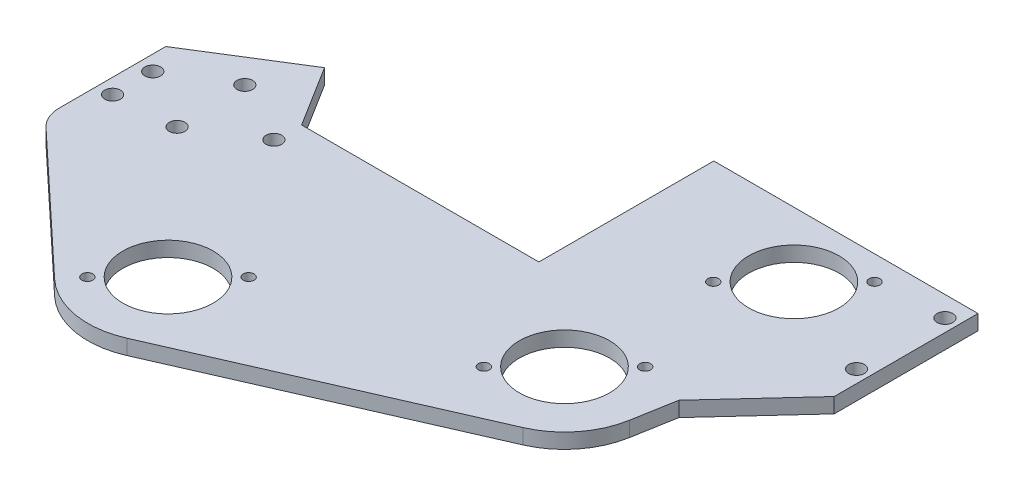
SolidWorks part; units mm, degrees
ref_plane "Front Plane" through (0, 0, 0) normal (0, 0, 1) x (1, 0, 0)
ref_plane "Top Plane" through (0, 0, 0) normal (0, 1, 0) x (1, 0, 0)
ref_plane "Right Plane" through (0, 0, 0) normal (1, 0, 0) x (0, 0, -1)
sketch "Sketch1" plane through (0, 0, 0) normal (0, 1, 0) x (1, 0, 0)
  line L1 (-62.0382, -79.8833) -> (25.1671, -41.6958)
  line L5 (39.9402, -22.8907) -> (42.2751, -9.5867)
  line L6 (42.2751, -9.5867) -> (65.831, 16.0128)
  line L12 (-135.7544, -31.9237) -> (-135.7544, 6.1763)
  line L16 (-92.7762, 6.1643) -> (-17.7344, 6.1643)
  line L17 (-135.7544, -31.9237) -> (-89.5888, -75.1562)
  line L19 (65.831, 61.4936) -> (-17.7344, 61.4936)
  line L20 (65.831, 16.0128) -> (65.831, 61.4936)
  line L22 (-17.7344, 61.4936) -> (-17.7344, 6.1643)
  line L23 (-135.7544, 6.1763) -> (-104.8504, 25.4872)
  line L24 (-218.6325, 207.5765) -> (-71.6498, -27.6449) construction
  line L25 (-104.8504, 25.4872) -> (-92.7762, 6.1643)
  line L26 (-72.2583, -56.6285) -> (15.031, -18.5085) construction
  line L27 (-72.2269, -82.0164) -> (109.3231, -82.0164) construction
  line L28 (15.0167, -18.5164) -> (15.0167, -82.0164) construction
  circle A0 centre (28.0466, 41.0458) radius 14.29
  circle A1 centre (15.031, -18.5085) radius 14.29
  circle A2 centre (-72.2583, -56.6285) radius 14.29
  arc A4 (39.9402, -22.8907) -> (25.1671, -41.6958) centre (15.0167, -18.5164) cw
  arc A6 (-62.0382, -79.8833) -> (-89.5888, -75.1562) centre (-72.2269, -56.6164) cw
  circle A7 centre (15.031, -18.5085) radius 25.4 construction
  circle A8 centre (-72.2583, -56.6285) radius 25.4 construction
  circle A9 centre (-28.6137, -37.5685) radius 22.225 construction
  circle A10 centre (28.0466, 41.0458) radius 30.48 construction
  circle A11 centre (15.031, -18.5085) radius 30.48 construction
  point P11 (-62.0382, -79.8833)
  point P34 (15.0167, -18.5164)
  point P35 (28.0466, 41.0458)
  dimension "D2" = 50.8
  dimension "D3" = 50.8
  dimension "D4" = 44.45
  dimension "D5" = 63.5
  dimension "D7" = 60.96
  dimension "D8" = 60.96
  dimension "D1" = 140.0048
  dimension "D6" = 95.25
  dimension "D9" = 50.8
  dimension "D10" = 143.51
extrude "Boss-Extrude1" add sketch "Sketch1" along normal blind 4.7625
fillet "Fillet1" radius 10 1 edges at (-135.7544, 2.3813, 31.9237)
hole_wizard "#10 Clearance Hole1" positions "Sketch2" profile "Sketch3" hole size "#10" standard "ANSI Inch" end condition through all
sketch "Sketch2" plane through (0, 4.7625, 0) normal (0, 1, 0) x (1, 0, 0)
  point P0 (61.8305, 55.0158)
  point P3 (61.8305, 27.0758)
  point P7 (-130.9919, -2.7257)
  point P10 (-130.9919, -15.4257)
sketch "Sketch3" plane through (61.8305, 4.7625, -55.0158) normal (1, 0, 0) x (0, 0, 1)
  line L0 (0, 0) -> (0, 4.7625)
  line L1 (0, 4.7625) -> (2.4892, 4.7625)
  line L2 (2.4892, 4.7625) -> (2.4892, 0)
  line L5 (2.4892, 0) -> (0, 0)
  line L11 (0, -6.35) -> (0, 107.95) construction
  dimension "Thru Hole Dia." = 4.9784
  dimension "Thru Hole Depth" = 4.7625
sketch "Sketch4" plane through (0, 4.7625, 0) normal (0, 1, 0) x (1, 0, 0)
  line L0 (-72.2583, -56.6285) -> (-102.5432, -8.1625) construction
  line L1 (-102.5432, -8.1625) -> (-93.1193, -2.2738) construction
  line L2 (-102.5432, -8.1625) -> (-111.9672, -14.0512) construction
  line L3 (-102.5432, -8.1625) -> (-112.7324, 8.1436) construction
  line L4 (-102.5432, -8.1625) -> (-174.2713, 106.6264) construction
  line L5 (65.831, 41.0458) -> (65.831, 28.3458) construction
  dimension "D1" = 57.15
  dimension "D2" = 22.225
  dimension "D3" = 32
hole_wizard "#10 Clearance Hole2" positions "Sketch5" profile "Sketch6" hole size "#10" standard "ANSI Inch" end condition through all
sketch "Sketch5" plane through (0, 4.7625, 0) normal (0, 1, 0) x (1, 0, 0)
  point P0 (-111.9672, -14.0512)
  point P3 (-93.1193, -2.2738)
  point P7 (-112.7324, 8.1436)
sketch "Sketch6" plane through (-111.9672, 4.7625, 14.0512) normal (1, 0, 0) x (0, 0, 1)
  line L0 (0, 0) -> (0, 4.7625)
  line L1 (0, 4.7625) -> (2.4892, 4.7625)
  line L2 (2.4892, 4.7625) -> (2.4892, 0)
  line L5 (2.4892, 0) -> (0, 0)
  line L11 (0, -6.35) -> (0, 107.95) construction
  dimension "Thru Hole Dia." = 4.9784
  dimension "Thru Hole Depth" = 4.7625
sketch "Sketch7" plane through (0, 4.7625, 0) normal (0, 1, 0) x (1, 0, 0)
  line L0 (-85.0103, -69.3804) -> (-59.5064, -43.8765) construction
  line L1 (2.279, -31.2604) -> (27.783, -5.7565) construction
  line L3 (15.2946, 28.2939) -> (40.7985, 53.7978) construction
  point P7 (-72.2583, -56.6285)
  point P11 (15.031, -18.5085)
  point P13 (28.0466, 41.0458)
hole_wizard "Tap Drill for #8-32 Tap1" positions "Sketch8" profile "Sketch9" hole size "#8-32" standard "ANSI Inch" end condition through all
sketch "Sketch8" plane through (0, 4.7625, 0) normal (0, 1, 0) x (1, 0, 0)
  point P0 (-59.5064, -43.8765)
  point P3 (-85.0103, -69.3804)
  point P6 (2.279, -31.2604)
  point P9 (27.783, -5.7565)
  point P12 (15.2946, 28.2939)
  point P15 (40.7985, 53.7978)
sketch "Sketch9" plane through (-59.5064, 4.7625, 43.8765) normal (1, 0, 0) x (0, 0, 1)
  line L0 (0, 0) -> (0, 4.7625)
  line L1 (0, 4.7625) -> (1.7272, 4.7625)
  line L2 (1.7272, 4.7625) -> (1.7272, 0)
  line L5 (1.7272, 0) -> (0, 0)
  line L11 (0, -6.35) -> (0, 107.95) construction
  dimension "Thru Hole Dia." = 3.4544
  dimension "Thru Hole Depth" = 4.7625
